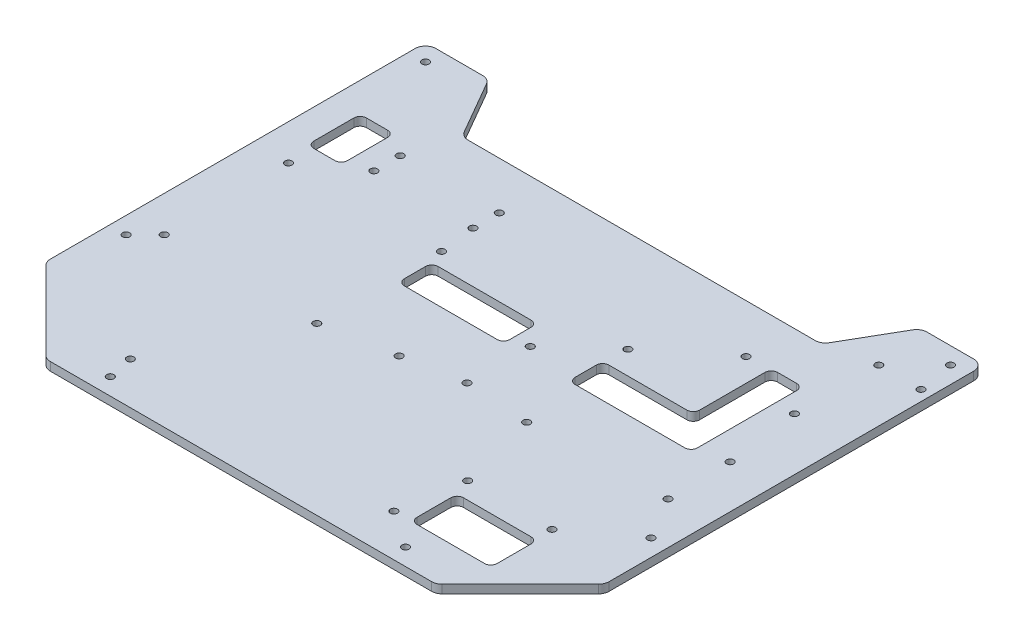
SolidWorks part; units mm, degrees
material "Acier non allié"
ref_plane "Front" through (0, 0, 0) normal (0, 0, 1) x (1, 0, 0)
ref_plane "Top" through (0, 0, 0) normal (0, 1, 0) x (1, 0, 0)
ref_plane "Right" through (0, 0, 0) normal (1, 0, 0) x (0, 0, -1)
sketch "Main scetch" plane through (0, 0, 0) normal (0, 1, 0) x (1, 0, 0)
  line L1 (0, 0) -> (132.5, 0) construction
  line L2 (0, 0) -> (0, 220) construction
  line L3 (0, 220) -> (132.5, 220) construction
  line L4 (132.5, 0) -> (132.5, 220) construction
  line L13 (-92.5, 0) -> (92.5, 0)
  line L14 (92.5, 0) -> (132.5, 40)
  line L15 (132.5, 40) -> (132.5, 220)
  line L16 (132.5, 220) -> (102.5, 220)
  line L17 (102.5, 220) -> (85.1795, 190)
  line L18 (85.1795, 190) -> (-85.1795, 190)
  line L19 (-102.5, 220) -> (-85.1795, 190)
  line L20 (-132.5, 220) -> (-102.5, 220)
  line L21 (-132.5, 40) -> (-132.5, 220)
  line L22 (-92.5, 0) -> (-132.5, 40)
  point P11 (0, 190)
  dimension "132.5" = 132.5
  dimension "D2" = 220
  dimension "D1" = 40
  dimension "D3" = 40
  dimension "D4" = 30
  dimension "D5" = 60
  dimension "D6" = 30
extrude "Main extrusion" add sketch "Main scetch" along normal blind 4
fillet "Congé1" radius 5 10 edges at (-132.5, 2, -40) (-92.5, 2, 0) (92.5, 2, 0) (132.5, 2, -40) (132.5, 2, -220) (102.5, 2, -220) (85.1795, 2, -190) (-85.1795, 2, -190) (-102.5, 2, -220) (-132.5, 2, -220)
sketch "Esquisse1" plane through (0, 4, 0) normal (0, 1, 0) x (1, 0, 0)
  line L0 (0, 0) -> (0, 218.5516) construction
  line L1 (132.5, 42.0711) -> (132.5, 215) construction
  line L2 (127.5, 220) -> (105.3868, 220) construction
  line L3 (-90.4289, 0) -> (90.4289, 0) construction
  circle A0 centre (70, 8) radius 1
  circle A1 centre (124.5, 70) radius 1
  circle A2 centre (124.5, 212) radius 1
  circle A3 centre (-124.5, 212) radius 1
  circle A4 centre (-124.5, 70) radius 1
  circle A5 centre (-70, 8) radius 1
  dimension "D1" = 2
  dimension "D2" = 2
  dimension "D3" = 2
  dimension "D4" = 8
  dimension "D5" = 8
  dimension "D6" = 8
  dimension "D7" = 8
  dimension "D8" = 70
  dimension "D9" = 70
extrude "Enlèv. mat.-Extru.1" cut sketch "Esquisse1" against normal through all
hole_wizard "Dégagement M31" positions "Esquisse2" profile "Esquisse3" hole size "M3" standard "ISO" end condition through all
sketch "Esquisse2" plane through (0, 4, 0) normal (0, 1, 0) x (1, 0, 0)
  point P0 (-124.5, 212)
  point P3 (-124.5, 70)
  point P6 (-70, 8)
  point P9 (70, 8)
  point P12 (124.5, 70)
  point P15 (124.5, 212)
sketch "Esquisse3" plane through (-124.5, 4, -212) normal (1, 0, 0) x (0, 0, 1)
  line L0 (0, 0) -> (0, 4)
  line L1 (0, 4) -> (1.7, 4)
  line L2 (1.7, 4) -> (1.7, 0)
  line L5 (1.7, 0) -> (0, 0)
  line L11 (0, -6.35) -> (0, 107.95) construction
  dimension "Diamètre du perçage jusqu'au prochain" = 3.4
  dimension "Profondeur du perçage jusqu'au prochain" = 4
sketch "Esquisse4" plane through (0, 4, 0) normal (0, 1, 0) x (1, 0, 0)
  line L0 (-132.5, 215) -> (-132.5, 42.0711) construction
  line L2 (82.2927, 190) -> (-82.2927, 190) construction
  line L3 (132.5, 42.0711) -> (132.5, 215) construction
  line L4 (-90.4289, 0) -> (90.4289, 0) construction
  line L5 (127.5, 220) -> (105.3868, 220) construction
  circle A1 centre (-68.5, 185) radius 1 construction
  circle A5 centre (72.5, 167) radius 1
  circle A6 centre (41.5, 142) radius 1
  circle A7 centre (107.5, 155) radius 1
  circle A8 centre (127.5, 195) radius 1
  circle A9 centre (112, 120) radius 1
  circle A10 centre (112.5, 90) radius 1
  circle A11 centre (17.2, 120) radius 1
  circle A12 centre (17.2, 90) radius 1
  circle A13 centre (47.5, 88) radius 1
  circle A14 centre (57.5, 50) radius 1
  circle A15 centre (97.5, 50) radius 1
  circle A16 centre (52.5, 20) radius 1
  circle A17 centre (-10, 85) radius 1
  circle A18 centre (-72.5, 20) radius 1
  circle A19 centre (107.5, 195) radius 1
  circle A23 centre (-115.5, 138) radius 1
  circle A24 centre (-42.86, 138) radius 1
  circle A25 centre (-115.5, 79.07) radius 1
  circle A26 centre (-42.8904, 78.82) radius 1
  circle A27 centre (-92, 167.5) radius 1
  circle A28 centre (-45, 167.5) radius 1
  circle A29 centre (-92, 155) radius 1
  circle A30 centre (-45, 155) radius 1
  dimension "D4" = 2
  dimension "D13" = 2
  dimension "D16" = 2
  dimension "D19" = 2
  dimension "D24" = 2
  dimension "D25" = 2
  dimension "D28" = 2
  dimension "D30" = 2
  dimension "D32" = 2
  dimension "D36" = 2
  dimension "D37" = 2
  dimension "D40" = 2
  dimension "D48" = 2
  dimension "D49" = 2
  dimension "D50" = 2
  dimension "D52" = 2
  dimension "D11" = 2
  dimension "D12" = 2
  dimension "D65" = 2
  dimension "D66" = 2
  dimension "D58" = 2
  dimension "D61" = 2
  dimension "D70" = 2
  dimension "D71" = 2
  dimension "D14" = 205
  dimension "D15" = 23
  dimension "D20" = 25
  dimension "D21" = 65
  dimension "D22" = 5
  dimension "D23" = 25
  dimension "D26" = 20.5
  dimension "D27" = 100
  dimension "D29" = 30
  dimension "D31" = 115.3
  dimension "D33" = 115.3
  dimension "D34" = 132
  dimension "D35" = 85
  dimension "D38" = 50
  dimension "D39" = 75
  dimension "D41" = 35
  dimension "D42" = 80
  dimension "D43" = 20
  dimension "D44" = 20
  dimension "D45" = 205
  dimension "D46" = 85
  dimension "D47" = 142.5
  dimension "D51" = 25
  dimension "D53" = 25
  dimension "D54" = 5
  dimension "D55" = 64
  dimension "D7" = 59.18
  dimension "D8" = 72.64
  dimension "D9" = 58.93
  dimension "D10" = 72.61
  dimension "D67" = 17
  dimension "D68" = 138
  dimension "D56" = 23.5
  dimension "D57" = 23.5
  dimension "D59" = 17.5
  dimension "D60" = 17.5
  dimension "D62" = 12.5
  dimension "D63" = 12.5
  dimension "D64" = 23.5
  dimension "D69" = 23.5
  dimension "D17" = 25
  dimension "D18" = 31
extrude "Enlèv. mat.-Extru.2" cut sketch "Esquisse4" against normal through all
hole_wizard "Dégagement M32" positions "Esquisse5" profile "Esquisse6" hole size "M3" standard "ISO" end condition through all
sketch "Esquisse5" plane through (0, 4, 0) normal (0, 1, 0) x (1, 0, 0)
  point P9 (17.2, 120)
  point P18 (41.5, 142)
  point P21 (72.5, 167)
  point P24 (107.5, 155)
  point P27 (127.5, 195)
  point P30 (112, 120)
  point P33 (112.5, 90)
  point P36 (47.5, 88)
  point P39 (17.2, 90)
  point P42 (57.5, 50)
  point P45 (97.5, 50)
  point P48 (-10, 85)
  point P51 (-72.5, 20)
  point P54 (52.5, 20)
  point P57 (107.5, 195)
  point P86 (-115.5, 138)
  point P89 (-42.86, 138)
  point P92 (-115.5, 79.07)
  point P95 (-42.8904, 78.82)
  point P102 (-92, 167.5)
  point P105 (-92, 155)
  point P108 (-45, 155)
  point P111 (-45, 167.5)
sketch "Esquisse6" plane through (17.2, 4, -120) normal (1, 0, 0) x (0, 0, 1)
  line L0 (0, 0) -> (0, 4)
  line L1 (0, 4) -> (1.7, 4)
  line L2 (1.7, 4) -> (1.7, 0)
  line L5 (1.7, 0) -> (0, 0)
  line L11 (0, -6.35) -> (0, 107.95) construction
  dimension "Diamètre du perçage jusqu'au prochain" = 3.4
  dimension "Profondeur du perçage jusqu'au prochain" = 4
sketch "Esquisse7" plane through (0, 4, 0) normal (0, 1, 0) x (1, 0, 0)
  line L0 (-90.4289, 0) -> (90.4289, 0) construction
  line L1 (-40.5, 131) -> (9.5, 131)
  line L2 (-40.5, 131) -> (-40.5, 115)
  line L3 (-40.5, 115) -> (9.5, 115)
  line L4 (9.5, 131) -> (9.5, 115)
  line L5 (-132.5, 215) -> (-132.5, 42.0711) construction
  line L8 (40.5, 115) -> (98.5, 115)
  line L10 (132.5, 42.0711) -> (132.5, 215) construction
  line L11 (40.5, 115) -> (40.5, 131)
  line L12 (83.5, 168) -> (98.5, 168)
  line L13 (83.5, 168) -> (83.5, 131)
  line L15 (98.5, 168) -> (98.5, 115)
  line L16 (40.5, 131) -> (83.5, 131)
  line L17 (-105.3868, 220) -> (-127.5, 220) construction
  line L18 (60.5, 42) -> (98.5, 42)
  line L19 (60.5, 42) -> (60.5, 20)
  line L20 (60.5, 20) -> (98.5, 20)
  line L21 (98.5, 42) -> (98.5, 20)
  line L22 (-118.5, 175) -> (-102.5, 175)
  line L23 (-118.5, 175) -> (-118.5, 150)
  line L24 (-118.5, 150) -> (-102.5, 150)
  line L25 (-102.5, 175) -> (-102.5, 150)
  dimension "D1" = 50
  dimension "D2" = 16
  dimension "D3" = 131
  dimension "D4" = 92
  dimension "D5" = 16
  dimension "D6" = 53
  dimension "D7" = 43
  dimension "D8" = 115
  dimension "D9" = 72
  dimension "D10" = 38
  dimension "D11" = 34
  dimension "D12" = 15
  dimension "D13" = 22
  dimension "D14" = 20
  dimension "D15" = 30
  dimension "D16" = 70
  dimension "D17" = 16
  dimension "D18" = 25
extrude "Enlèv. mat.-Extru.3" cut sketch "Esquisse7" against normal up to surface (4 mm away) up to face at (17.2, 0, -118.3)
fillet "Congé2" radius 3 18 edges at (60.5, 2, -42) (60.5, 2, -20) (98.5, 2, -20) (98.5, 2, -42) (98.5, 2, -168) (98.5, 2, -115) (83.5, 2, -168) (40.5, 2, -131) (83.5, 2, -131) (40.5, 2, -115) (-40.5, 2, -115) (9.5, 2, -115) (9.5, 2, -131) (-40.5, 2, -131) (-118.5, 2, -150) (-102.5, 2, -150) (-102.5, 2, -175) (-118.5, 2, -175)
equation "\"WIDTH\"= 300mm'Total width of the robot"
equation "\"LENGTH\"= 220mm'Total length of the robot"
equation "\"D2@Main scetch\" = \"LENGTH\""
equation "\"CUT_DEPTH\"= 45mm'Depth of the cut on the edges of the plate"
equation "\"Plate_th\"= 3mm'Thickness of the plate"
equation "\"D1\"= \"Plate_th\""
equation "\"D47@Esquisse4\"=(80+205)/2"
